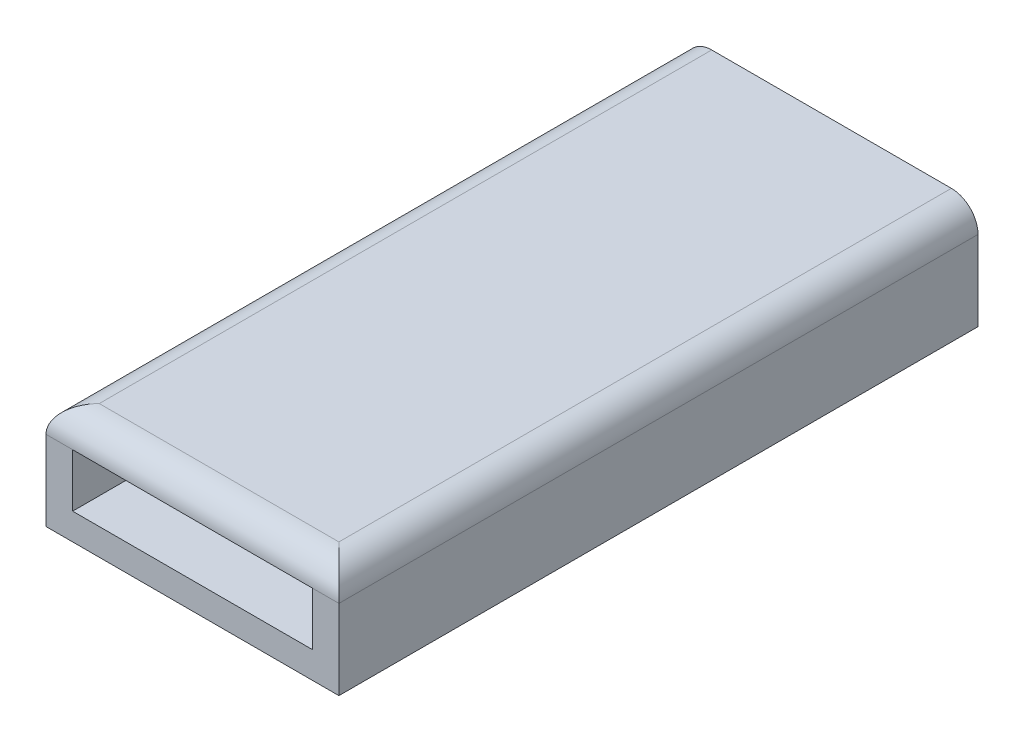
SolidWorks part; units mm, degrees
ref_plane "Front Plane" through (0, 0, 0) normal (0, 0, 1) x (1, 0, 0)
ref_plane "Top Plane" through (0, 0, 0) normal (0, 1, 0) x (1, 0, 0)
ref_plane "Right Plane" through (0, 0, 0) normal (1, 0, 0) x (0, 0, -1)
sketch "Sketch1" plane through (0, 0, 0) normal (0, 0, 1) x (1, 0, 0)
  line L1 (-17.4625, -6.35) -> (17.4625, -6.35)
  line L2 (-17.4625, -6.35) -> (-17.4625, 6.35)
  line L3 (-17.4625, 6.35) -> (17.4625, 6.35)
  line L4 (17.4625, -6.35) -> (17.4625, 6.35)
  line L5 (-17.4625, -6.35) -> (17.4625, 6.35) construction
  line L6 (-17.4625, 6.35) -> (17.4625, -6.35) construction
  point P0 (0, 0)
  dimension "D1" = 34.925
  dimension "D2" = 12.7
extrude "Boss-Extrude1" add sketch "Sketch1" along normal blind 76.2
sketch "Sketch2" plane through (0, 0, 76.2) normal (0, 0, 1) x (1, 0, 0)
  line L0 (17.4625, 6.35) -> (-17.4625, 6.35) construction
  line L1 (-14.2875, -3.175) -> (14.2875, -3.175)
  line L2 (-14.2875, -3.175) -> (-14.2875, 3.175)
  line L3 (-14.2875, 3.175) -> (14.2875, 3.175)
  line L4 (14.2875, -3.175) -> (14.2875, 3.175)
  line L5 (-14.2875, -3.175) -> (14.2875, 3.175) construction
  line L6 (-14.2875, 3.175) -> (14.2875, -3.175) construction
  line L7 (17.4625, -6.35) -> (17.4625, 6.35) construction
  point P0 (0, 0)
  dimension "D1" = 3.175
  dimension "D2" = 3.175
extrude "Cut-Extrude1" cut sketch "Sketch2" against normal blind 74.93
fillet "Fillet1" radius 3.175 3 edges at (0, 6.35, 76.2) (17.4625, 6.35, 38.1) (-17.4625, 6.35, 38.1)
